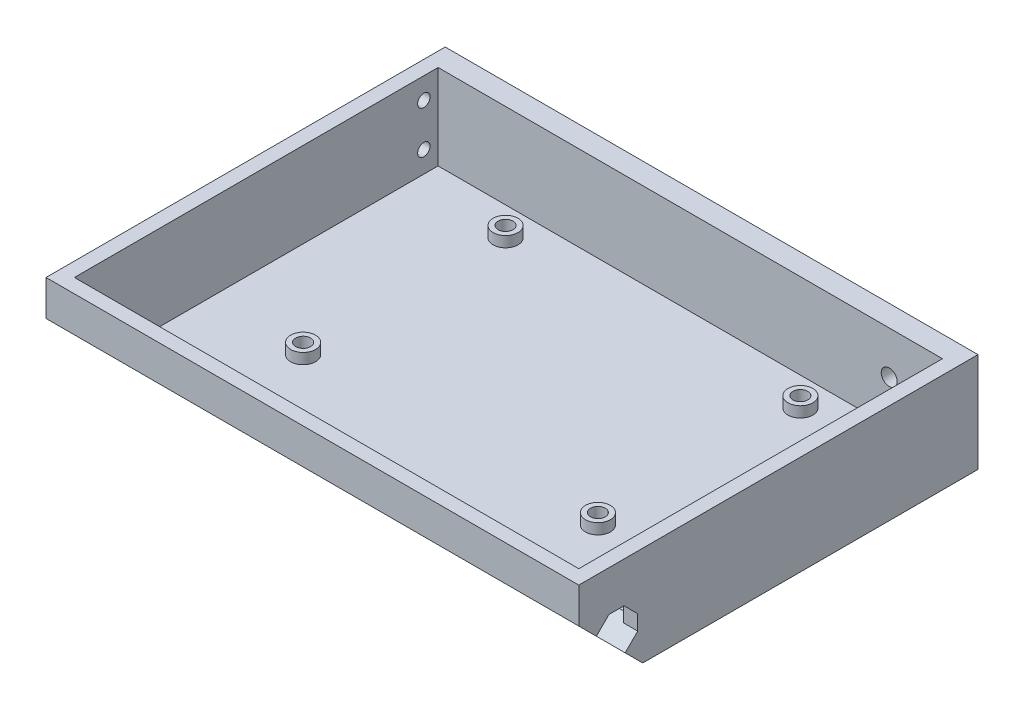
SolidWorks part; units mm, degrees
ref_plane "Front Plane" through (0, 0, 0) normal (0, 0, 1) x (1, 0, 0)
ref_plane "Top Plane" through (0, 0, 0) normal (0, 1, 0) x (1, 0, 0)
ref_plane "Right Plane" through (0, 0, 0) normal (1, 0, 0) x (0, 0, -1)
sketch "Sketch1" plane through (0, 0, 0) normal (1, 0, 0) x (0, 0, -1)
  line L1 (-14, 14) -> (14, 14)
  line L2 (-14, 14) -> (-14, -14)
  line L3 (-14, -14) -> (14, -14)
  line L4 (14, 14) -> (14, -14)
  line L5 (-14, 14) -> (14, -14) construction
  line L6 (-14, -14) -> (14, 14) construction
  point P0 (0, 0)
  dimension "D1" = 28
  dimension "D2" = 28
extrude "Boss-Extrude1" add sketch "Sketch1" along normal blind 120 and the other way blind 30
chamfer "Chamfer1" distance 18 angle 45 1 edges at (45, -14, 14)
sketch "Sketch2" plane through (0, 0, -14) normal (0, 0, -1) x (-1, 0, 0)
  line L4 (30, -14) -> (30, 14)
  line L5 (30, 14) -> (-120, 14)
  line L6 (-120, 14) -> (-120, -14)
  line L7 (-120, -14) -> (30, -14)
  line L8 (30, -14) -> (30, 14)
  line L9 (30, 14) -> (-120, 14)
  line L10 (-120, 14) -> (-120, -14)
  line L11 (-120, -14) -> (30, -14)
  dimension "D1" = 0
extrude "Boss-Extrude2" add sketch "Sketch2" along normal blind 100
sketch "Sketch3" plane through (0, 14, 0) normal (0, 1, 0) x (1, 0, 0)
  line L0 (-30, 114) -> (-30, -14) construction
  line L1 (-26, 110) -> (116, 110)
  line L2 (-26, 110) -> (-26, 10)
  line L3 (-26, 10) -> (116, 10)
  line L4 (116, 110) -> (116, 10)
  dimension "D1" = 4
  dimension "D2" = 4
  dimension "D3" = 4
  dimension "D4" = 100
extrude "Cut-Extrude1" cut sketch "Sketch3" against normal blind 24
sketch "Sketch4" plane through (0, 14, 0) normal (0, 1, 0) x (1, 0, 0)
  line L1 (-26, 10) -> (116, 10)
  line L2 (-26, 10) -> (-26, -10)
  line L3 (-26, -10) -> (116, -10)
  line L4 (116, 10) -> (116, -10)
  dimension "D1" = 4
  dimension "D2" = 4
extrude "Cut-Extrude2" cut sketch "Sketch4" against normal blind 4
chamfer "Chamfer2" distance 20 angle 45 1 edges at (45, 10, -10)
sketch "Sketch6" plane through (0, -5, 5) normal (0, -0.7071, 0.7071) x (1, 0, 0)
  line L0 (-30, 12.7279) -> (120, 12.7279) construction
  line L1 (120, 12.7279) -> (120, -12.7279) construction
  circle A0 centre (34, 10) radius 1.75
  circle A1 centre (17.9966, 10) radius 1.75
  circle A2 centre (56, 10) radius 1.75
  circle A3 centre (72, 10) radius 1.75
  circle A4 centre (72, -10) radius 1.75
  circle A5 centre (56, -10) radius 1.75
  circle A6 centre (34, -10) radius 1.75
  circle A7 centre (17.9966, -10) radius 1.75
  point P28 (45, 12.7279)
  point P31 (120, 0)
  dimension "D1" = 3.5
  dimension "D2" = 16
  dimension "D3" = 22
  dimension "D4" = 16.0034
  dimension "D5" = 20
  dimension "D6" = 11
  dimension "D7" = 10
extrude "Cut-Extrude3" cut sketch "Sketch6" against normal through all
sketch "Sketch10" plane through (0, 14, 0) normal (0, 1, 0) x (1, 0, 0)
  line L0 (-79.4783, 98.3833) -> (131.5217, 98.3833) construction
  line L1 (135.0296, 124.2015) -> (-30, 124.2015)
  line L2 (135.0296, 124.2015) -> (135.0296, 98.3833)
  line L3 (135.0296, 98.3833) -> (-30, 98.3833)
  line L4 (-30, 124.2015) -> (-30, 98.3833)
  line L5 (-30, 114) -> (-30, -14) construction
  point P8 (102.2158, 119.4621)
  point P9 (-10, 119.2112)
  point P10 (135.0296, 124.2015)
extrude "Cut-Extrude7" cut sketch "Sketch10" against normal through all
sketch "Sketch11" plane through (-30, 0, 0) normal (-1, 0, 0) x (0, 0, 1)
  line L0 (9.0503, -0.9497) -> (3.3934, 4.7071)
  line L1 (-4, -14) -> (14, 4) construction
  line L2 (3.3934, 4.7071) -> (-4.7071, -3.3934)
  line L3 (-4.7071, -3.3934) -> (0.9497, -9.0503)
  line L4 (0.9497, -9.0503) -> (9.0503, -0.9497)
  dimension "D1" = 7
  dimension "D2" = 7
  dimension "D3" = 8
extrude "Cut-Extrude8" cut sketch "Sketch11" against normal through all
chamfer "Chamfer3" distance 3 angle 45 2 edges at (-28, 4.7071, 3.3934) (-28, -3.3934, -4.7071)
sketch "Sketch12" plane through (0, -5, 5) normal (0, -0.7071, 0.7071) x (-1, 0, 0)
  line L0 (-120, -5.7279) -> (30, -5.7279) construction
  line L1 (26, -5.7279) -> (-116, -5.7279)
  line L2 (26, -5.7279) -> (26, 5.7279)
  line L3 (26, 5.7279) -> (-116, 5.7279)
  line L4 (-116, -5.7279) -> (-116, 5.7279)
  line L5 (-120, 5.7279) -> (30, 5.7279) construction
  dimension "D1" = 4
  dimension "D2" = 4
extrude "Cut-Extrude9" cut sketch "Sketch12" against normal through all
sketch "Sketch13" plane through (0, -10, 0) normal (0, 1, 0) x (1, 0, 0)
  line L0 (116, 10) -> (116, 98.3833) construction
  line L1 (-26, 98.3833) -> (116, 98.3833)
  line L2 (-26, 98.3833) -> (-26, 92.3833)
  line L3 (-26, 92.3833) -> (116, 92.3833)
  line L4 (116, 98.3833) -> (116, 92.3833)
  dimension "D1" = 6
extrude "Boss-Extrude4" add sketch "Sketch13" along normal up to surface (24 mm away) up to face at (45, 14, -43.1916)
sketch "Sketch14" plane through (0, 0, -98.3833) normal (0, 0, -1) x (-1, 0, 0)
  circle A0 centre (-101, 2) radius 2.25
  dimension "D2" = 4.5
  dimension "D1" = 131
  dimension "D3" = 16
extrude "Cut-Extrude10" cut sketch "Sketch14" against normal blind 6
sketch "Sketch15" plane through (-26, 0, 0) normal (1, 0, 0) x (0, 0, -1)
  circle A0 centre (88.3833, 8) radius 1.75
  circle A1 centre (88.3833, -4) radius 1.75
  point P4 (0, 0)
  dimension "D2" = 3.5
  dimension "D1" = 12
  dimension "D3" = 10
  dimension "D4" = 10
extrude "Cut-Extrude11" cut sketch "Sketch15" against normal through all
sketch "Sketch17" plane through (0, -10, 0) normal (0, 1, 0) x (1, 0, 0)
  circle A0 centre (1, 84.3833) radius 3.5
  circle A1 centre (84, 84.3833) radius 3.5
  circle A2 centre (84, 27.3833) radius 3.5
  circle A3 centre (1, 27.3833) radius 3.5
  point P8 (0, 0)
  point P9 (0, 0)
  point P10 (0, 0)
  point P11 (0, 0)
  point P12 (87.8537, 87.7161)
  point P13 (-26, 92.3833)
  point P16 (0, 0)
  point P17 (1.1627, 87.3359)
  point P18 (2.04, 23.1427)
  point P19 (0, 0)
  point P21 (0.8236, 25.4789)
  dimension "D1" = 7
  dimension "D4" = 32
  dimension "D2" = 57
  dimension "D3" = 83
  dimension "D5" = 8
extrude "Boss-Extrude5" add sketch "Sketch17" along normal blind 3
sketch "Sketch18" plane through (0, -7, 0) normal (0, 1, 0) x (1, 0, 0)
  circle A0 centre (84, 84.3833) radius 2.1
  circle A1 centre (84, 27.3833) radius 2.1
  circle A2 centre (1, 27.3833) radius 2.1
  circle A3 centre (1, 84.3833) radius 2.1
  dimension "D1" = 4.2
extrude "Cut-Extrude12" cut sketch "Sketch18" against normal blind 6
